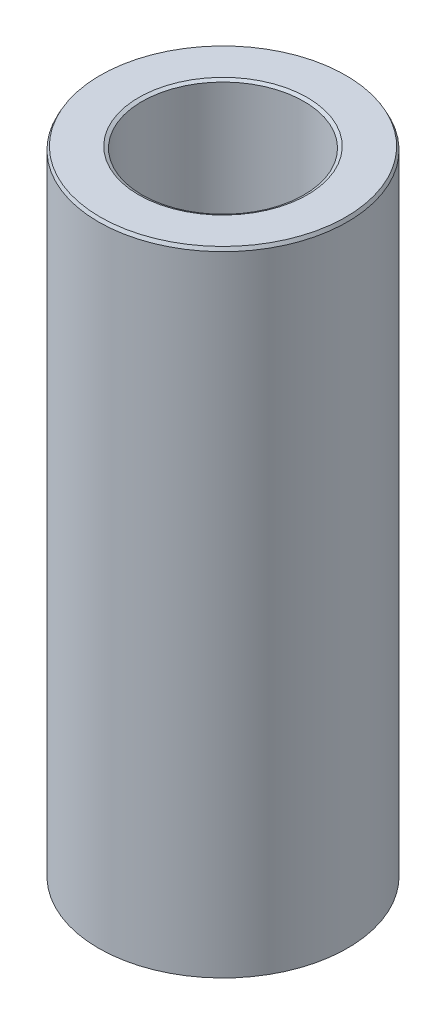
SolidWorks part; units mm, degrees
ref_plane "Front Plane" through (0, 0, 0) normal (0, 0, 1) x (1, 0, 0)
ref_plane "Top Plane" through (0, 0, 0) normal (0, 1, 0) x (1, 0, 0)
ref_plane "Right Plane" through (0, 0, 0) normal (1, 0, 0) x (0, 0, -1)
sketch "Sketch1" plane through (0, 0, 0) normal (0, 1, 0) x (1, 0, 0)
  circle A0 centre (0, 0) radius 30
  dimension "SLEEVE_OD" = 60
extrude "Boss-Extrude1" add sketch "Sketch1" along normal blind 152.7861
sketch "Sketch2" plane through (0, 0, 0) normal (0, 1, 0) x (1, 0, 0)
  circle A0 centre (0, 0) radius 19.5193
  dimension "BORE_D" = 39.0385
extrude "Cut-Extrude1" cut sketch "Sketch2" along normal through all
chamfer "Chamfer1" distance 0.8058 angle 26.976 4 edges at (0, 152.7861, 19.5193) (0, 0, 19.5193) (0, 0, 30) (0, 152.7861, 30) first distance on face at (0, 152.7861, 19.5193) first distance on face at (0, 0, 19.5193) first distance on face at (0, 152.7861, 30)
